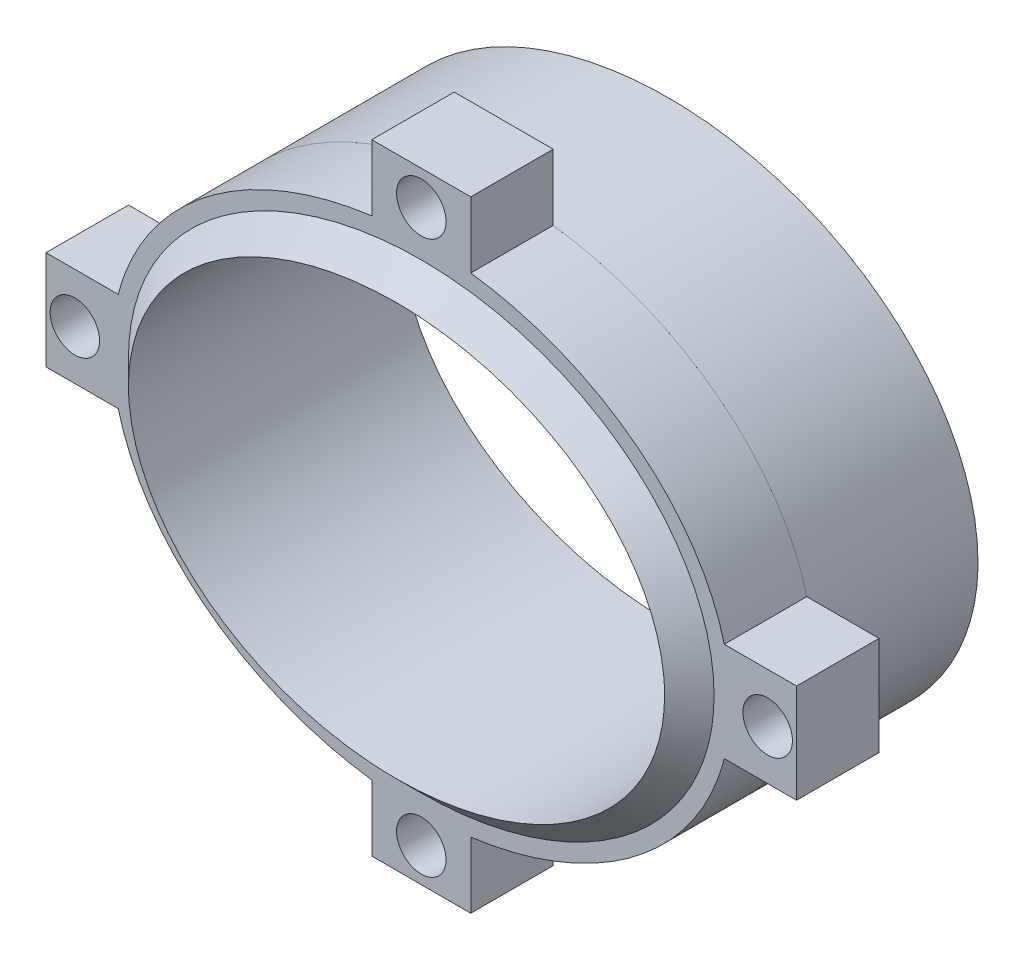
SolidWorks part; units mm, degrees
ref_plane "Alzado" through (0, 0, 0) normal (0, 0, 1) x (1, 0, 0)
ref_plane "Planta" through (0, 0, 0) normal (0, 1, 0) x (1, 0, 0)
ref_plane "Vista lateral" through (0, 0, 0) normal (1, 0, 0) x (0, 0, -1)
sketch "Sketch1" plane through (0, 0, 0) normal (0, 0, 1) x (1, 0, 0)
  line L0 (0, 40.4956) -> (0, 30) construction
  line L1 (-6, 29.6135) -> (-6, 37.6135)
  line L2 (-6, 37.6135) -> (0, 37.6135)
  line L3 (0, 37.6135) -> (6, 37.6135)
  line L4 (6, 37.6135) -> (6, 29.6135)
  line L5 (-37.5, 0) -> (37.5, 0) construction
  line L6 (6, -37.6135) -> (6, -29.6135)
  line L7 (0, -37.6135) -> (6, -37.6135)
  line L8 (-6, -37.6135) -> (0, -37.6135)
  line L9 (-6, -29.6135) -> (-6, -37.6135)
  line L10 (-37.5, 0) -> (-45.5, 0) construction
  line L11 (-36.7423, 6) -> (-45.5, 6)
  line L12 (-45.5, 6) -> (-45.5, -6)
  line L13 (-36.7423, -6) -> (-45.5, -6)
  line L14 (0, 0) -> (0, 15.1486) construction
  line L15 (36.7423, -6) -> (45.5, -6)
  line L16 (45.5, 6) -> (45.5, -6)
  line L17 (36.7423, 6) -> (45.5, 6)
  circle A0 centre (0, 33.5) radius 3
  circle A1 centre (0, -33.5) radius 3
  circle A2 centre (-42, 0) radius 3
  circle A3 centre (42, 0) radius 3
  ellipse E0 centre (0, 0) end of major axis (-37.5, 0) minor radius 30 (-6, 29.6135) -> (-36.7423, 6) ccw
  ellipse E1 centre (0, 0) end of major axis (-37.5, 0) minor radius 30 (6, -29.6135) -> (36.7423, -6) ccw
  ellipse E2 centre (0, 0) end of major axis (-37.5, 0) minor radius 30 (36.7423, 6) -> (6, 29.6135) ccw
  ellipse E3 centre (0, 0) end of major axis (-37.5, 0) minor radius 30 (-36.7423, -6) -> (-6, -29.6135) ccw
  point P9 (-6, 29.6135)
  point P10 (6, 29.6135)
  point P20 (-36.7423, 6)
  point P21 (-36.7423, -6)
  point P39 (36.7423, -6)
  point P41 (36.7423, 6)
  dimension "D6" = 6
  dimension "D11" = 6
  dimension "D1" = 30
  dimension "D2" = 37.5
  dimension "D3" = 6
  dimension "D4" = 6
  dimension "D5" = 8
  dimension "D7" = 3.5
  dimension "D8" = 8
  dimension "D9" = 6
  dimension "D10" = 6
  dimension "D12" = 4.5
extrude "Boss-Extrude1" add sketch "Sketch1" along normal blind 10
sketch "Sketch2" plane through (0, 0, 0) normal (0, 0, 1) x (1, 0, 0)
  ellipse E0 centre (0, 0) end of major axis (37.5, 0) minor radius 30.0005
  ellipse E1 centre (0, 0) end of major axis (32.5, 0) minor radius 25 construction
  dimension "D1" = 30.0005
  dimension "D2" = 37.5
  dimension "D3" = 25
  dimension "D4" = 32.5
extrude "Boss-Extrude2" add sketch "Sketch2" against normal blind 20
sketch "Sketch4" plane through (0, 0, 10) normal (0, 0, 1) x (1, 0, 0)
  ellipse E0 centre (0, 0) end of major axis (-37.5, 0) minor radius 30 construction
  ellipse E1 centre (0, 0) end of major axis (-35.5, 0) minor radius 28
  ellipse E2 centre (0, 0) end of major axis (-30.5, 0) minor radius 23
  dimension "D1" = 30
  dimension "D2" = 37.5
  dimension "D3" = 28
  dimension "D4" = 35.5
  dimension "D5" = 23
  dimension "D6" = 30.5
extrude "Boss-Extrude3" add sketch "Sketch4" along normal blind 3
chamfer "Chamfer1" distance 3 angle 45 1 edges at (-35.5, 0, 13)
sketch "Sketch3" plane through (0, 0, 10) normal (0, 0, 1) x (1, 0, 0)
  ellipse E0 centre (0, 0) end of major axis (-32.5, 0) minor radius 25
  dimension "D1" = 25
extrude "Cut-Extrude1" cut sketch "Sketch3" against normal mid plane 68
